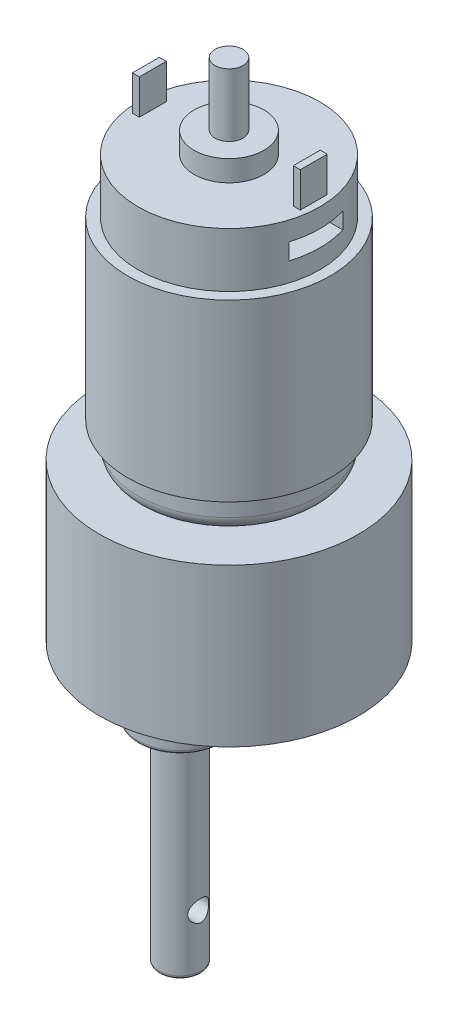
SolidWorks part; units mm, degrees
ref_plane "Front Plane" through (0, 0, 0) normal (0, 0, 1) x (1, 0, 0)
ref_plane "Top Plane" through (0, 0, 0) normal (0, 1, 0) x (1, 0, 0)
ref_plane "Right Plane" through (0, 0, 0) normal (1, 0, 0) x (0, 0, -1)
sketch "Sketch1" plane through (0, 0, 0) normal (0, 1, 0) x (1, 0, 0)
  circle A0 centre (0, 0) radius 18.5
  dimension "D1" = 37
extrude "Boss-Extrude1" add sketch "Sketch1" along normal blind 22.5
sketch "Sketch2" plane through (0, 22.5, 0) normal (0, 1, 0) x (1, 0, 0)
  circle A0 centre (0, 0) radius 13
  dimension "D1" = 26
extrude "Boss-Extrude2" add sketch "Sketch2" along normal blind 37.8 separate body
ref_plane "Plane1" through (0, 27.5, 0) normal (0, 1, 0) x (1, 0, 0)
sketch "Sketch3" plane through (0, 27.5, 0) normal (0, 1, 0) x (1, 0, 0)
  circle A0 centre (0, 0) radius 14.5
  dimension "D1" = 29
extrude "Boss-Extrude3" add sketch "Sketch3" along normal blind 25
fillet "Fillet1" radius 2 1 edges at (0, 22.5, 13)
sketch "Sketch4" plane through (0, 0, 0) normal (0, -1, 0) x (1, 0, 0)
  circle A0 centre (0, 7) radius 6
  dimension "D2" = 12
  dimension "D1" = 7
extrude "Boss-Extrude4" add sketch "Sketch4" along normal blind 6.3
fillet "Fillet2" radius 0.5 1 edges at (0, -6.3, 1)
sketch "Sketch5" plane through (0, -6.3, 0) normal (0, -1, 0) x (1, 0, 0)
  circle A0 centre (0, 7) radius 3
  dimension "D1" = 6
extrude "Boss-Extrude5" add sketch "Sketch5" along normal blind 30 separate body
fillet "Fillet3" radius 0.5 1 edges at (0, -36.3, 4)
sketch "Sketch6" plane through (0, 0, 0) normal (1, 0, 0) x (0, 0, -1)
  line L0 (-7, -36.3) -> (-7, -28.3) construction
  line L1 (-9.5, -36.3) -> (-4.5, -36.3) construction
  circle A0 centre (-7, -28.3) radius 1.5
  point P6 (0, 0)
  dimension "D2" = 3
  dimension "D1" = 8
extrude "Cut-Extrude1" cut sketch "Sketch6" against normal blind 30 and the other way blind 30
sketch "Sketch7" plane through (0, 0, 0) normal (1, 0, 0) x (0, 0, -1)
  line L0 (0, 60.3) -> (0, 52.5) construction
  line L1 (-3.8558, 57.5782) -> (3.8558, 57.5782)
  line L2 (-3.8558, 57.5782) -> (-3.8558, 55.2218)
  line L3 (-3.8558, 55.2218) -> (3.8558, 55.2218)
  line L4 (3.8558, 57.5782) -> (3.8558, 55.2218)
  line L5 (-3.8558, 57.5782) -> (3.8558, 55.2218) construction
  line L6 (-3.8558, 55.2218) -> (3.8558, 57.5782) construction
  line L7 (13, 60.3) -> (-13, 60.3) construction
  line L8 (14.5, 52.5) -> (-14.5, 52.5) construction
  point P0 (0, 56.4)
  point P5 (0, 0)
extrude "Cut-Extrude2" cut sketch "Sketch7" against normal blind 30 and the other way blind 30
sketch "Sketch8" plane through (0, 60.3, 0) normal (0, 1, 0) x (1, 0, 0)
  circle A0 centre (0, 0) radius 5
  dimension "D1" = 10
extrude "Boss-Extrude6" add sketch "Sketch8" along normal blind 3
sketch "Sketch9" plane through (0, 63.3, 0) normal (0, 1, 0) x (1, 0, 0)
  circle A0 centre (0, 0) radius 2
  dimension "D1" = 4
extrude "Boss-Extrude7" add sketch "Sketch9" along normal blind 9
sketch "Sketch10" plane through (0, 60.3, 0) normal (0, 1, 0) x (1, 0, 0)
  line L0 (11.5, 2.044) -> (11.5, -1.8104) construction
  line L1 (12, 2.044) -> (11, 2.044)
  line L2 (12, 2.044) -> (12, -1.8104)
  line L3 (12, -1.8104) -> (11, -1.8104)
  line L4 (11, 2.044) -> (11, -1.8104)
  line L5 (0, 0) -> (0, -10.9169) construction
  line L6 (-11.5, 2.044) -> (-11.5, -1.8104) construction
  line L7 (-11, 2.044) -> (-11, -1.8104)
  line L8 (-12, -1.8104) -> (-11, -1.8104)
  line L9 (-12, 2.044) -> (-12, -1.8104)
  line L10 (-12, 2.044) -> (-11, 2.044)
  dimension "D1" = 1
  dimension "D2" = 11.5
extrude "Boss-Extrude8" add sketch "Sketch10" along normal blind 5 separate body
sketch "Sketch11" plane through (0, 0, 0) normal (0, -1, 0) x (1, 0, 0)
  line L0 (-18.5, 0) -> (18.5, 0) construction
  line L1 (-7.75, 13.4234) -> (7.75, -13.4234) construction
  line L2 (7.75, 13.4234) -> (-7.75, -13.4234) construction
  circle A0 centre (0, 0) radius 15.5 construction
  circle A1 centre (0, 0) radius 18.5 construction
  point P9 (0, 0)
  point P12 (0, 0)
  point P14 (0, 0)
  point P15 (15.5, 0)
  point P16 (-7.75, 13.4234)
  point P17 (7.75, 13.4234)
  point P18 (-7.75, -13.4234)
  point P19 (7.75, -13.4234)
  point P20 (-15.5, 0)
  dimension "D1" = 31
  dimension "D2" = 120
  dimension "D3" = 120
hole_wizard "M3 Tapped Hole1" positions "3DSketch1" profile "Sketch12" tap size "M3" standard "ISO"
sketch3d "3DSketch1"
  point P0 (-15.5, 0, 0)
  point P3 (-7.75, 0, 13.4234)
  point P6 (7.75, 0, 13.4234)
  point P9 (15.5, 0, 0)
  point P12 (7.75, 0, -13.4234)
  point P15 (-7.75, 0, -13.4234)
sketch "Sketch12" plane through (-15.5, 0, 0) normal (1, 0, 0) x (0, 0, -1)
  line L0 (0, 0) -> (0, 4.2511)
  line L1 (0, 4.2511) -> (1.25, 3.5)
  line L2 (1.25, 3.5) -> (1.25, 0)
  line L5 (1.25, 0) -> (0, 0)
  line L10 (0, 4.2511) -> (-1.25, 3.5) construction
  line L11 (0, -6.35) -> (0, 107.95) construction
  dimension "Tap Drill Dia." = 2.5
  dimension "Tap Drill Depth" = 3.5
  dimension "Drill Angle" = 118
cosmetic thread "Hole Thread1" parameters "D1"=3.5, "D2"=3
cosmetic thread "Hole Thread2" parameters "D1"=3.5, "D2"=3
cosmetic thread "Hole Thread3" parameters "D1"=3.5, "D2"=3
cosmetic thread "Hole Thread4" parameters "D1"=3.5, "D2"=3
cosmetic thread "Hole Thread5" parameters "D1"=3.5, "D2"=3
cosmetic thread "Hole Thread6" parameters "D1"=3.5, "D2"=3
